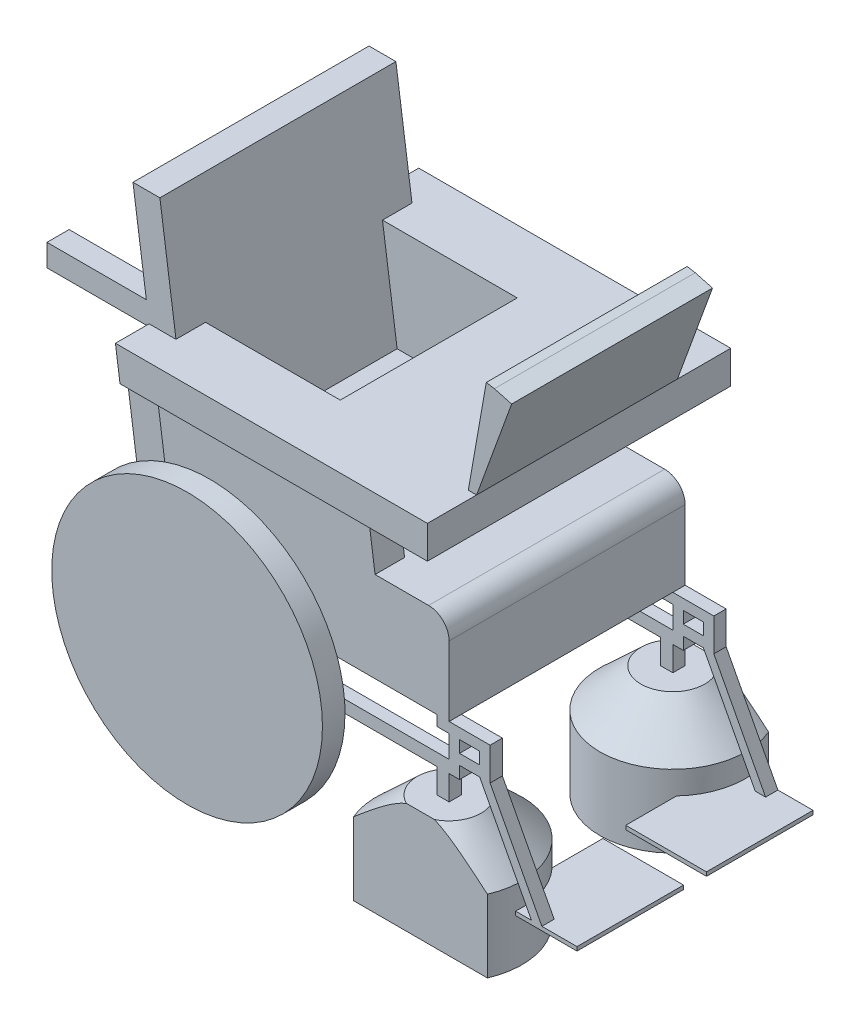
SolidWorks part; units mm, degrees
ref_plane "Front Plane" through (0, 0, 0) normal (0, 0, 1) x (1, 0, 0)
ref_plane "Top Plane" through (0, 0, 0) normal (0, 1, 0) x (1, 0, 0)
ref_plane "Right Plane" through (0, 0, 0) normal (1, 0, 0) x (0, 0, -1)
sketch "Sketch1" plane through (0, 0, 0) normal (0, 0, 1) x (1, 0, 0)
  line L0 (330.2, 660.4) -> (330.2, 0)
  line L1 (0, 0) -> (660.4, 0)
  line L2 (0, 0) -> (0, 660.4)
  line L3 (0, 660.4) -> (660.4, 660.4)
  line L4 (660.4, 0) -> (660.4, 660.4)
  line L5 (660.4, 330.2) -> (0, 330.2)
  circle A0 centre (330.2, 330.2) radius 330.2
  dimension "D1" = 660.4
sketch3d "3DSketch1" plane through (0, 0, 0) normal (0, 0, 1) x (1, 0, 0)
  dimension "D1" = 685.8
sketch "Sketch2" plane through (0, 0, -685.8) normal (0, 0, 1) x (1, 0, 0)
  line L0 (330.2, 660.4) -> (330.2, 0)
  line L1 (0, 0) -> (660.4, 0)
  line L2 (0, 0) -> (0, 660.4)
  line L3 (0, 660.4) -> (660.4, 660.4)
  line L4 (660.4, 0) -> (660.4, 660.4)
  line L5 (660.4, 330.2) -> (0, 330.2)
  circle A0 centre (330.2, 330.2) radius 330.2
  dimension "D1" = 660.4
extrude "Boss-Extrude1" add sketch "Sketch1" against normal blind 55 contours A0
extrude "Boss-Extrude2" add sketch "Sketch2" along normal blind 55 separate body contours A0
sketch3d "3DSketch3"
  line L0 (0, 0, -685.8) -> (0, 0, 0)
  line L1 (0, 0, -342.9) -> (500, 0, -342.9)
  line L2 (0, 0, -342.9) -> (0, 500, -342.9)
  dimension "D1" = 500
  dimension "D2" = 500
sketch3d "3DSketch2"
  line L0 (330.2, 460, -630.8) -> (330.2, 460, -685.8)
  line L1 (330.2, 460, -630.8) -> (750.2, 460, -630.8)
  line L2 (330.2, 460, -630.8) -> (330.2, 460, -55)
  line L3 (330.2, 460, -55) -> (750.2, 460, -55)
  line L4 (750.2, 460, -630.8) -> (750.2, 460, -55)
  line L5 (330.2, 460, -55) -> (330.2, 460, 0)
  line L7 (330.2, 660.4, -685.8) -> (330.2, 0, -685.8) construction
  line L8 (330.2, 660.4, 0) -> (330.2, 0, 0) construction
  line L9 (330.2, 460, -630.8) -> (265.2, 460, -630.8)
  line L10 (330.2, 460, -630.8) -> (330.2, 460, -55)
  line L11 (330.2, 460, -55) -> (265.2, 460, -55)
  line L12 (265.2, 460, -630.8) -> (265.2, 460, -55)
  dimension "D1" = 460
  dimension "D2" = 420
  dimension "D3" = 65
extrude "Boss-Extrude3" add sketch "3DSketch2" along direction (0, -1, 0) on the side against the normal blind 10 contours L3 L4 L1 L2 | L9 L12 L11 L10
sketch "Sketch4" plane through (0, -170.8, -630.8) normal (0, 0, 1) x (1, 0, 0)
  line L0 (208.8289, 1364.6) -> (330.2, 501)
  line L1 (208.8289, 1364.6) -> (143.1901, 1364.6)
  line L2 (330.2, 501) -> (265.8326, 491.9537)
  line L3 (143.1901, 1364.6) -> (265.8326, 491.9537)
  line L5 (330.2, 501) -> (660.4, 501)
  line L6 (0, 170.8) -> (500, 170.8) construction
  circle A0 centre (330.2, 501) radius 330.2 construction
  point P0 (330.2, 501)
  dimension "D1" = 65
  dimension "D2" = 1193.8
  dimension "D3" = 98
extrude "Boss-Extrude6" add sketch "Sketch4" along normal up to surface (575.8 mm away) contours L2 L3 L1 L0 up to face at (206.0942, 396.3454, -55)
sketch "Sketch25" plane through (0, 0, -342.9) normal (0, 0, 1) x (1, 0, 0)
  line L0 (576.8393, 834.4) -> (259.3393, 834.4)
  line L1 (943.5393, 914.4) -> (576.8393, 914.4)
  line L2 (943.5393, 914.4) -> (943.5393, 834.4)
  line L3 (943.5393, 834.4) -> (576.8393, 834.4)
  line L4 (576.8393, 914.4) -> (576.8393, 834.4)
  line L6 (208.8289, 1193.8) -> (330.2, 330.2)
  dimension "D1" = 80
  dimension "D2" = 317.5
  dimension "D3" = 366.7
  dimension "D4" = 914.4
extrude "Boss-Extrude33" add sketch "Sketch25" along normal blind 370 and the other way blind 370 contours L1 L4 L3 L2 region at (760.1893, 874.4, -342.9)
sketch "Sketch5" plane through (0, 470, 0) normal (0, 1, 0) x (1, 0, 0)
  line L0 (310.5524, 55) -> (760.5524, 55)
  line L1 (310.5524, 55) -> (310.5524, 127)
  line L2 (760.5524, 55) -> (760.5524, 127)
  line L3 (310.5524, 127) -> (760.5524, 127)
  line L4 (310.5524, 55) -> (629.3454, 55) construction
  line L5 (310.5524, 630.8) -> (760.5524, 630.8)
  line L6 (310.5524, 630.8) -> (310.5524, 558.8)
  line L7 (760.5524, 630.8) -> (760.5524, 558.8)
  line L8 (310.5524, 558.8) -> (760.5524, 558.8)
  line L9 (310.5524, 630.8) -> (629.3454, 630.8) construction
  line L11 (310.5524, 630.8) -> (310.5524, 55) construction
  line L12 (310.5524, 55) -> (310.5524, 630.8) construction
  dimension "D1" = 431.8
  dimension "D2" = 450
extrude "Boss-Extrude7" add sketch "Sketch5" along direction (0.1392, -0.9903, 0) on the side of the normal up to surface (364.4 mm away) up to face at (760.1893, 834.4, -342.9)
sketch "Sketch8" plane through (0, 0, -630.8) normal (0, 0, -1) x (-1, 0, 0)
  line L0 (-1140.7, 120.65) -> (-1226.425, 120.65)
  line L1 (-330.2, 660.4) -> (-330.2, 330.2)
  line L2 (-939.8, 360.2) -> (-330.2, 360.2)
  line L3 (-939.8, 360.2) -> (-939.8, 330.2)
  line L4 (-939.8, 330.2) -> (-330.2, 330.2)
  line L5 (-330.2, 360.2) -> (-330.2, 330.2)
  line L6 (-989, 360.2) -> (-989, 385.6)
  line L7 (-914.4, 330.2) -> (-884.4, 330.2)
  line L8 (-914.4, 330.2) -> (-914.4, 270.2)
  line L9 (-914.4, 270.2) -> (-884.4, 270.2)
  line L10 (-884.4, 330.2) -> (-884.4, 270.2)
  line L11 (-939.8, 360.2) -> (-914.4, 360.2)
  line L12 (-939.8, 360.2) -> (-939.8, 440.2)
  line L13 (-939.8, 440.2) -> (-914.4, 440.2)
  line L14 (-914.4, 360.2) -> (-914.4, 440.2)
  line L15 (-1115.3, 120.65) -> (-1029.575, 120.65)
  line L16 (-939.8, 360.2) -> (-1014.4, 360.2)
  line L17 (-939.8, 360.2) -> (-939.8, 385.6)
  line L18 (-939.8, 385.6) -> (-1014.4, 385.6)
  line L19 (-1014.4, 360.2) -> (-1014.4, 385.6)
  line L20 (-1014.4, 385.6) -> (-989, 385.6)
  line L21 (-1014.4, 385.6) -> (-1014.4, 440.2)
  line L22 (-1014.4, 440.2) -> (-989, 440.2)
  line L23 (-989, 385.6) -> (-989, 440.2)
  line L24 (-989, 440.2) -> (-939.8, 440.2)
  line L25 (-989, 440.2) -> (-989, 414.8)
  line L26 (-989, 414.8) -> (-939.8, 414.8)
  line L27 (-939.8, 440.2) -> (-939.8, 414.8)
  line L28 (-1014.4, 360.2) -> (-1140.7, 120.65)
  line L29 (-1140.7, 120.65) -> (-1115.3, 120.65)
  line L30 (-1115.3, 120.65) -> (-989, 360.2)
  line L31 (-1029.575, 120.65) -> (-1029.575, 111.125)
  line L32 (-1029.575, 111.125) -> (-1226.425, 111.125)
  line L33 (-1226.425, 111.125) -> (-1226.425, 120.65)
  line L34 (-330.2, 360.2) -> (-325.9838, 360.2)
  line L35 (-939.8, 440.2) -> (-330.2, 440.2)
  line L36 (-939.8, 440.2) -> (-939.8, 660.4)
  line L37 (-939.8, 660.4) -> (-330.2, 660.4)
  line L38 (-330.2, 440.2) -> (-330.2, 660.4)
  line L39 (-311.9578, 460) -> (-330.2, 330.2) construction
  line L40 (-325.9838, 360.2) -> (-330.2, 330.2)
  line L41 (-330.2, 330.2) -> (-259.3393, 834.4)
  line L43 (-914.4, 440.2) -> (-884.4, 440.2)
  line L44 (-914.4, 440.2) -> (-914.4, 414.8)
  line L45 (-330.2, 660.4) -> (-283.7934, 660.4)
  line L46 (-330.2, 440.2) -> (-314.7405, 440.2)
  line L47 (-914.4, 660.4) -> (-914.4, 440.2)
  line L48 (-914.4, 414.8) -> (-884.4, 414.8)
  line L49 (-884.4, 440.2) -> (-884.4, 414.8)
  arc A1 (-633.8182, 460) -> (-220.7768, 641.7423) centre (-330.2, 330.2) ccw construction
  point P4 (-1128, 111.125)
  point P5 (0, 0)
  point P39 (-899.4, 270.2)
  line M2 (-750.2, 460) -> (-633.8182, 460)
  arc M3 (-633.8182, 460) -> (-220.7768, 641.7423) centre (-330.2, 330.2) cw
  line M8 (-709.3393, 834.4) -> (-760.5524, 470)
  line M9 (-760.5524, 470) -> (-750.2, 470)
  line M10 (-750.2, 470) -> (-750.2, 460)
  dimension "D1" = 30
  dimension "D2" = 330.2
  dimension "D3" = 609.6
  dimension "D4" = 25.4
  dimension "D5" = 30
  dimension "D6" = 60
  dimension "D7" = 80
  dimension "D8" = 25.4
  dimension "D9" = 25.4
  dimension "D10" = 25.4
  dimension "D11" = 25.4
  dimension "D12" = 9.525
  dimension "D13" = 196.85
  dimension "D14" = 228.6
  dimension "D15" = 120.65
  dimension "D16" = 100
  dimension "D17" = 660.4
extrude "Boss-Extrude13" add sketch "Sketch8" against normal blind 30 contours L3 | L2 L14 L13 L12 | L23 L26 L12 L24 | L18 L23 L22 L21 | L19 L16 L6 L18 | L12 L18 L6 L16 | L40 L34 L1 | L49 L35 L14 L48 | L3 L4 L5 L2 | L9 L10 L7 L8 region at (1001.7, 372.9, -630.8) region at (964.4, 372.9, -630.8) region at (1001.7, 412.9, -630.8) region at (927.1, 400.2, -630.8) region at (964.4, 427.5, -630.8) region at (328.7946, 350.2, -630.8) region at (899.4, 427.5, -630.8)
sketch "Sketch19" plane through (0, 270.2, 0) normal (0, -1, 0) x (1, 0, 0)
  line L0 (899.4, -630.8) -> (899.4, -600.8)
  line L1 (914.4, -630.8) -> (884.4, -630.8) construction
  line L2 (914.4, -600.8) -> (884.4, -600.8) construction
  circle A0 centre (899.4, -615.8) radius 177.8
  point P6 (899.4, -615.8)
  dimension "D1" = 355.6
extrude "Boss-Extrude22" add sketch "Sketch19" along normal up to surface (270.2 mm away) contours A0 up to plane "Top Plane"
chamfer "Chamfer1" distance 100 angle 43 1 edges at (899.4, 270.2, -793.6) first distance on face at (899.4, 270.2, -615.8)
extrude "Boss-Extrude27" add sketch "Sketch8<7>" against normal blind 30 contours L29 L30 L16 L28 region at (1064.85, 240.425, -630.8)
sketch "Sketch8<7>" plane through (0, 0, -630.8) normal (0, 0, -1) x (-1, 0, 0) same geometry as "Sketch8"
extrude "Boss-Extrude20" add sketch "Sketch8<4>" against normal blind 260 contours L33 L32 L31 L15 L29 L0 region at (1128, 115.8875, -630.8)
sketch "Sketch8<4>" plane through (0, 0, -630.8) normal (0, 0, -1) x (-1, 0, 0) same geometry as "Sketch8"
sketch "Sketch23" plane through (0, 0, -55) normal (0, 0, -1) x (-1, 0, 0)
  line L0 (-1140.7, 120.65) -> (-1226.425, 120.65)
  line L1 (-330.2, 660.4) -> (-330.2, 330.2)
  line L2 (-939.8, 360.2) -> (-330.2, 360.2)
  line L3 (-939.8, 360.2) -> (-939.8, 330.2)
  line L4 (-939.8, 330.2) -> (-330.2, 330.2)
  line L5 (-330.2, 360.2) -> (-330.2, 330.2)
  line L6 (-989, 360.2) -> (-989, 385.6)
  line L7 (-914.4, 330.2) -> (-884.4, 330.2)
  line L8 (-914.4, 330.2) -> (-914.4, 270.2)
  line L9 (-914.4, 270.2) -> (-884.4, 270.2)
  line L10 (-884.4, 330.2) -> (-884.4, 270.2)
  line L11 (-939.8, 360.2) -> (-914.4, 360.2)
  line L12 (-939.8, 360.2) -> (-939.8, 440.2)
  line L13 (-939.8, 440.2) -> (-914.4, 440.2)
  line L14 (-914.4, 360.2) -> (-914.4, 440.2)
  line L15 (-1115.3, 120.65) -> (-1029.575, 120.65)
  line L16 (-939.8, 360.2) -> (-1014.4, 360.2)
  line L17 (-939.8, 360.2) -> (-939.8, 385.6)
  line L18 (-939.8, 385.6) -> (-1014.4, 385.6)
  line L19 (-1014.4, 360.2) -> (-1014.4, 385.6)
  line L20 (-1014.4, 385.6) -> (-989, 385.6)
  line L21 (-1014.4, 385.6) -> (-1014.4, 440.2)
  line L22 (-1014.4, 440.2) -> (-989, 440.2)
  line L23 (-989, 385.6) -> (-989, 440.2)
  line L24 (-989, 440.2) -> (-939.8, 440.2)
  line L25 (-989, 440.2) -> (-989, 414.8)
  line L26 (-989, 414.8) -> (-939.8, 414.8)
  line L27 (-939.8, 440.2) -> (-939.8, 414.8)
  line L28 (-1014.4, 360.2) -> (-1140.7, 120.65)
  line L29 (-1140.7, 120.65) -> (-1115.3, 120.65)
  line L30 (-1115.3, 120.65) -> (-989, 360.2)
  line L31 (-1029.575, 120.65) -> (-1029.575, 111.125)
  line L32 (-1029.575, 111.125) -> (-1226.425, 111.125)
  line L33 (-1226.425, 111.125) -> (-1226.425, 120.65)
  line L34 (-330.2, 360.2) -> (-325.9838, 360.2)
  line L35 (-939.8, 440.2) -> (-330.2, 440.2)
  line L36 (-939.8, 440.2) -> (-939.8, 550)
  line L37 (-939.8, 550) -> (-330.2, 550)
  line L38 (-330.2, 440.2) -> (-330.2, 550)
  line L39 (-311.9578, 460) -> (-330.2, 330.2) construction
  line L40 (-325.9838, 360.2) -> (-330.2, 330.2)
  line L42 (-914.4, 440.2) -> (-884.4, 440.2)
  line L43 (-914.4, 440.2) -> (-914.4, 414.8)
  line L44 (-914.4, 414.8) -> (-884.4, 414.8)
  line L45 (-884.4, 440.2) -> (-884.4, 414.8)
  circle A2 centre (-330.2, 330.2) radius 330.2 construction
  point P4 (-1128, 111.125)
  point P5 (0, 0)
  point P39 (-899.4, 270.2)
  arc M79 (-633.8182, 460) -> (-220.7768, 641.7423) centre (-330.2, 330.2) ccw
  line M103 (-330.2, 330.2) -> (-311.9578, 460)
  dimension "D1" = 30
  dimension "D2" = 330.2
  dimension "D3" = 609.6
  dimension "D4" = 25.4
  dimension "D5" = 30
  dimension "D6" = 60
  dimension "D7" = 80
  dimension "D8" = 25.4
  dimension "D9" = 25.4
  dimension "D10" = 25.4
  dimension "D11" = 25.4
  dimension "D12" = 9.525
  dimension "D13" = 196.85
  dimension "D14" = 228.6
  dimension "D15" = 120.65
  dimension "D16" = 100
  dimension "D17" = 550
extrude "Boss-Extrude28" add sketch "Sketch23" along normal blind 30 contours L4 L1 L2 M79 | L3 L4 L2 M79 | L10 L4 L8 L9 | L2 L14 L13 L12 | L12 L18 L6 L16 | L23 L26 L12 L24 | L18 L23 L22 L21 | L19 L16 L6 L18 | L34 L1 M103 | L45 L35 L14 L44 region at (1001.7, 372.9, -55) region at (964.4, 372.9, -55) region at (1001.7, 412.9, -55) region at (927.1, 400.2, -55) region at (799.8723, 345.2122, -55) region at (964.4, 427.5, -55) region at (495.0728, 345.1897, -55) region at (899.4, 427.5, -55) region at (899.4, 300.2, -55) region at (328.7946, 350.2, -55)
sketch "Sketch24" plane through (0, 270.2, 0) normal (0, -1, 0) x (-1, 0, 0)
  line L0 (-899.4, 55) -> (-899.4, 85)
  line L1 (-914.4, 55) -> (-884.4, 55) construction
  line L2 (-914.4, 85) -> (-884.4, 85) construction
  circle A0 centre (-899.4, 70) radius 177.8
  point P6 (-899.4, 70)
  dimension "D1" = 355.6
extrude "Boss-Extrude29" add sketch "Sketch24" along normal up to surface (270.2 mm away) contours A0 up to plane "Top Plane"
chamfer "Chamfer2" distance 100 angle 43 1 edges at (899.4, 270.2, -247.8) first distance on face at (899.4, 270.2, -70)
extrude "Boss-Extrude30" add sketch "Sketch23<10>" along normal blind 30 contours L29 L30 L16 L28 region at (1064.85, 240.425, -55)
sketch "Sketch23<10>" plane through (0, 0, -55) normal (0, 0, -1) x (-1, 0, 0) same geometry as "Sketch23"
extrude "Boss-Extrude31" add sketch "Sketch23<12>" along normal blind 260 contours L33 L32 L31 L15 L29 L0 region at (1128, 115.8875, -55)
sketch "Sketch23<12>" plane through (0, 0, -55) normal (0, 0, -1) x (-1, 0, 0) same geometry as "Sketch23"
sketch "Sketch16" plane through (0, 0, -630.8) normal (0, 0, -1) x (-1, 0, 0)
  line L0 (-143.1901, 1193.8) -> (-220.7768, 641.7423) construction
  line L5 (-183.3497, 908.05) -> (-183.3497, 962.025)
  line L6 (-183.3497, 962.025) -> (66.6503, 962.025)
  line L7 (-183.3497, 962.025) -> (-183.3497, 908.05)
  line L8 (-183.3497, 908.05) -> (66.6503, 908.05)
  line L9 (66.6503, 962.025) -> (66.6503, 908.05)
  dimension "D1" = 908.05
  dimension "D2" = 250
  dimension "D3" = 53.975
sketch "Sketch18" plane through (0, 0, -55) normal (0, 0, -1) x (-1, 0, 0)
  line L1 (-143.1901, 1193.8) -> (-220.7768, 641.7423) construction
  line L5 (-183.3497, 908.05) -> (-183.3497, 962.025)
  line L6 (-183.3497, 962.025) -> (66.6503, 962.025)
  line L7 (-183.3497, 962.025) -> (-183.3497, 908.05)
  line L8 (-183.3497, 908.05) -> (66.6503, 908.05)
  line L9 (66.6503, 962.025) -> (66.6503, 908.05)
  dimension "D1" = 908.05
  dimension "D2" = 250
  dimension "D3" = 53.975
extrude "Boss-Extrude18" add sketch "Sketch16" against normal blind 53.975 contours L9 L6 L5 L8 region at (58.3497, 935.0375, -630.8)
extrude "Boss-Extrude19" add sketch "Sketch18" along normal blind 53.975 contours L6 L9 L8 L5 | L5 region at (58.3497, 935.0375, -55)
extrude "Boss-Extrude32" add sketch "Sketch8<8>" against normal up to surface (575.8 mm away) contours L37 M8 M9 M10 M2 M3 | L37 L47 L35 L1 M3 M2 M10 M9 M8 | L1 L46 L41 M3 | L45 L41 M3 region at (607.3, 446.4432, -630.8) region at (313.5753, 567.989, -630.8) region at (636.3616, 577.4535, -630.8) region at (295.5533, 659.4352, -630.8) up to face at (293.9754, 299.5287, -55)
sketch "Sketch8<8>" plane through (0, 0, -630.8) normal (0, 0, -1) x (-1, 0, 0) same geometry as "Sketch8"
sketch "Sketch26" plane through (576.8393, 0, 0) normal (-1, 0, 0) x (0, 0, 1)
  line L0 (-712.9, 834.4) -> (27.1, 834.4) construction
  line L1 (-127, 834.4) -> (27.1, 834.4)
  line L2 (-127, 834.4) -> (-127, 914.4)
  line L3 (-127, 914.4) -> (27.1, 914.4)
  line L4 (27.1, 834.4) -> (27.1, 914.4)
  line L5 (-712.9, 914.4) -> (27.1, 914.4) construction
  line L6 (27.1, 914.4) -> (27.1, 834.4) construction
  line L8 (-712.9, 914.4) -> (-558.8, 914.4)
  line L9 (-712.9, 914.4) -> (-712.9, 834.4)
  line L10 (-712.9, 834.4) -> (-558.8, 834.4)
  line L11 (-558.8, 914.4) -> (-558.8, 834.4)
extrude "Boss-Extrude34" add sketch "Sketch26" along normal up to surface (383.1388 mm away) up to face at (192.5753, 842.4066, -342.9)
sketch "Sketch27" plane through (304.9446, 42.8572, 0) normal (-0.9903, -0.1392, 0) x (0, 0, 1)
  line L0 (-55, 281.0316) -> (-630.8, 281.0316) construction
  line L1 (-517.9, 281.0316) -> (-167.9, 281.0316)
  line L2 (-517.9, 281.0316) -> (-517.9, 681.0316)
  line L3 (-517.9, 681.0316) -> (-167.9, 681.0316)
  line L4 (-167.9, 281.0316) -> (-167.9, 681.0316)
  point P6 (-342.9, 281.0316)
  dimension "D1" = 350
  dimension "D2" = 400
extrude "Boss-Extrude35" add sketch "Sketch27" along normal blind 200
sketch "Sketch29" plane through (0, 0, -712.9) normal (0, 0, -1) x (-1, 0, 0)
  line L0 (-943.5393, 914.4) -> (-986.9514, 1160.6019)
  line L1 (-986.9514, 1160.6019) -> (-967.2552, 1164.0749)
  line L2 (-967.2552, 1164.0749) -> (-923.2308, 914.4)
  line L3 (-943.5393, 914.4) -> (-182.4573, 914.4) construction
  line L4 (-923.2308, 914.4) -> (-943.5393, 914.4)
  line L5 (-943.5393, 914.4) -> (-1029.0443, 1149.3232)
  line L6 (-1029.0443, 1149.3232) -> (-986.9514, 1160.6019)
  line M4 (-182.4573, 914.4) -> (-943.5393, 914.4)
  dimension "D1" = 20
  dimension "D2" = 250
  dimension "D3" = 100
  dimension "D4" = 250
  dimension "D5" = 110
extrude "Boss-Extrude36" add sketch "Sketch29" against normal blind 490 from offset 130 contours L6 L5 L0 | L2 L1 L0 M4 region at (986.5117, 1074.775, -712.9) region at (955.2208, 1038.3712, -712.9) offset against normal yes
fillet "Fillet3" radius 50 1 edges at (914.4, 660.4, -342.9)
sketch "Sketch30" plane through (0, 0, 0) normal (0, 0, 1) x (1, 0, 0)
  line L1 (-859.7351, 660.4) -> (1763.3884, 660.4)
  line L2 (-859.7351, 660.4) -> (-859.7351, -1730.0373)
  line L3 (-859.7351, -1730.0373) -> (1763.3884, -1730.0373)
  line L4 (1763.3884, 660.4) -> (1763.3884, -1730.0373)
  circle A0 centre (330.2, 330.2) radius 330.2 construction
sketch "Sketch31" plane through (0, 0, -685.8) normal (0, 0, -1) x (-1, 0, 0)
  line L1 (-2033.4337, 660.4) -> (551.3323, 660.4)
  line L2 (-2033.4337, 660.4) -> (-2033.4337, -1167.7476)
  line L3 (-2033.4337, -1167.7476) -> (551.3323, -1167.7476)
  line L4 (551.3323, 660.4) -> (551.3323, -1167.7476)
  circle A0 centre (-330.2, 330.2) radius 330.2 construction
extrude "Cut-Extrude1" cut sketch "Sketch30" along normal through all
extrude "Cut-Extrude2" cut sketch "Sketch31" along normal through all
